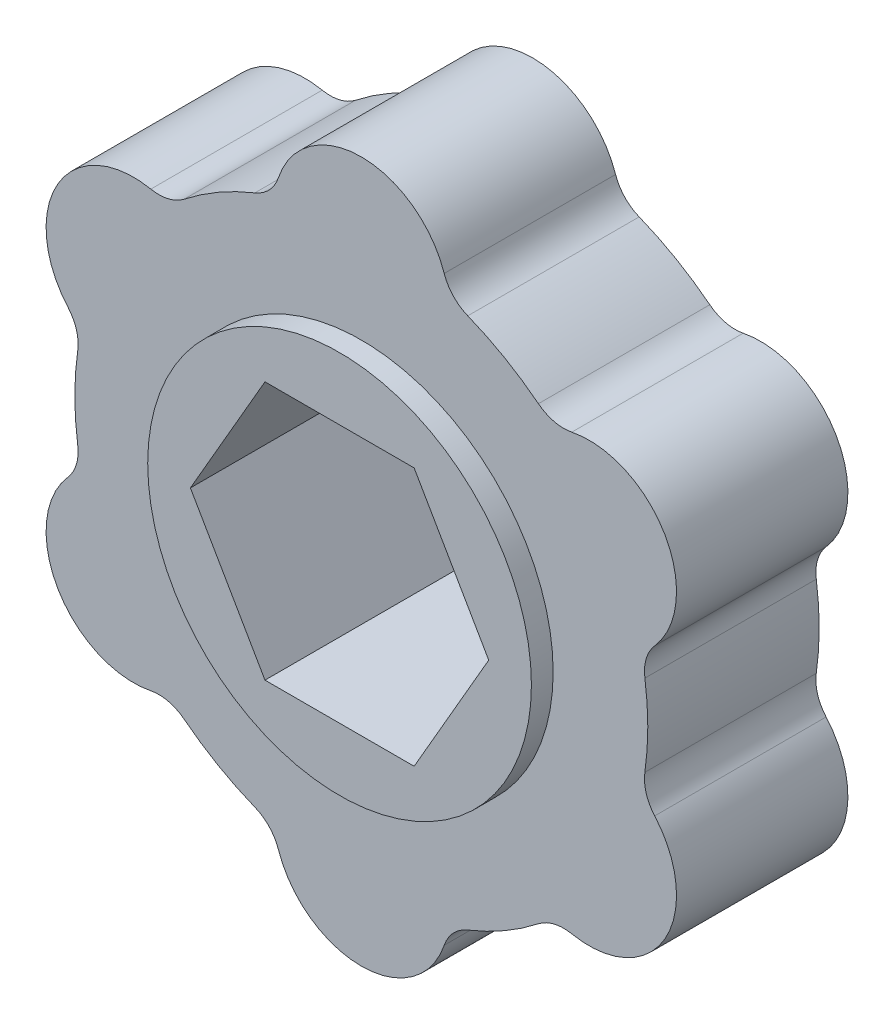
SolidWorks part; units mm, degrees
material "PET"
ref_plane "Front Plane" through (0, 0, 0) normal (0, 0, 1) x (1, 0, 0)
ref_plane "Top Plane" through (0, 0, 0) normal (0, 1, 0) x (1, 0, 0)
ref_plane "Right Plane" through (0, 0, 0) normal (1, 0, 0) x (0, 0, -1)
sketch "Sketch5" plane through (0, 0, 0) normal (0, 0, 1) x (1, 0, 0)
  line L0 (0, 0) -> (0, 13.0556) construction
  circle A0 centre (0, 0) radius 14.224
  circle A1 centre (0, 0) radius 17.399 construction
  arc A2 (-4.3147, 13.5538) -> (4.3147, 13.5538) centre (0, 13.0556) cw
  arc A3 (9.5806, 10.5136) -> (13.8953, 3.0402) centre (11.3065, 6.5278) cw
  arc A4 (13.8953, -3.0402) -> (9.5806, -10.5136) centre (11.3065, -6.5278) cw
  arc A5 (4.3147, -13.5538) -> (-4.3147, -13.5538) centre (0, -13.0556) cw
  arc A6 (-9.5806, -10.5136) -> (-13.8953, -3.0402) centre (-11.3065, -6.5278) cw
  arc A7 (-13.8953, 3.0402) -> (-9.5806, 10.5136) centre (-11.3065, 6.5278) cw
  point P24 (0, 0)
  dimension "D1" = 28.448
  dimension "D2" = 34.798
  dimension "D3" = 4.3434
  dimension "D4" = 6
extrude "Boss-Extrude2" add sketch "Sketch5" along normal blind 8.509 contours A7 A0 | A2 A0 | A3 A0 | A4 A0 | A5 A0 | A6 A0 | A0 region at (13.3495, 7.7073, 0) region at (13.3495, -7.7073, 0) region at (0, 15.4147, 0) region at (0, -15.4147, 0) region at (-13.3495, 7.7073, 0) region at (-13.3495, -7.7073, 0)
fillet "Fillet1" radius 2.032 12 edges at (-9.5806, 10.5136, 4.2545) (-4.3147, 13.5538, 4.2545) (4.3147, 13.5538, 4.2545) (9.5806, 10.5136, 4.2545) (13.8953, 3.0402, 4.2545) (13.8953, -3.0402, 4.2545) (9.5806, -10.5136, 4.2545) (4.3147, -13.5538, 4.2545) (-4.3147, -13.5538, 4.2545) (-9.5806, -10.5136, 4.2545) (-13.8953, -3.0402, 4.2545) (-13.8953, 3.0402, 4.2545)
sketch "Sketch6" plane through (0, 0, 8.509) normal (0, 0, 1) x (1, 0, 0)
  line L1 (7.4057, 0) -> (3.7028, 6.4135)
  line L2 (3.7028, 6.4135) -> (-3.7028, 6.4135)
  line L3 (-3.7028, 6.4135) -> (-7.4057, 0)
  line L4 (-7.4057, 0) -> (-3.7028, -6.4135)
  line L5 (-3.7028, -6.4135) -> (3.7028, -6.4135)
  line L6 (3.7028, -6.4135) -> (7.4057, 0)
  circle A0 centre (0, 0) radius 6.4135 construction
  dimension "D1" = 12.827
extrude "Cut-Extrude1" cut sketch "Sketch6" against normal through all
sketch "Sketch7" plane through (0, 0, 0) normal (0, 0, -1) x (-1, 0, 0)
  line L0 (-7.4057, 0) -> (-3.7028, 6.4135) construction
  line L1 (-3.7028, -6.4135) -> (-7.4057, 0) construction
  line L2 (3.7028, -6.4135) -> (-3.7028, -6.4135) construction
  line L3 (7.4057, 0) -> (3.7028, -6.4135) construction
  line L4 (3.7028, 6.4135) -> (7.4057, 0) construction
  line L5 (-3.7028, 6.4135) -> (3.7028, 6.4135) construction
  line L6 (-7.4057, 0) -> (-3.7028, 6.4135)
  line L7 (-3.7028, -6.4135) -> (-7.4057, 0)
  line L8 (3.7028, -6.4135) -> (-3.7028, -6.4135)
  line L9 (7.4057, 0) -> (3.7028, -6.4135)
  line L10 (3.7028, 6.4135) -> (7.4057, 0)
  line L11 (-3.7028, 6.4135) -> (3.7028, 6.4135)
  circle A0 centre (0, 0) radius 9.525
  dimension "D1" = 19.05
extrude "Boss-Extrude3" add sketch "Sketch7" along normal blind 1.0795
sketch "Sketch8" plane through (0, 0, 8.509) normal (0, 0, 1) x (1, 0, 0)
  line L1 (3.7028, -6.4135) -> (7.4057, 0)
  line L2 (7.4057, 0) -> (3.7028, 6.4135)
  line L3 (3.7028, 6.4135) -> (-3.7028, 6.4135)
  line L4 (-3.7028, 6.4135) -> (-7.4057, 0)
  line L5 (-7.4057, 0) -> (-3.7028, -6.4135)
  line L6 (-3.7028, -6.4135) -> (3.7028, -6.4135)
  circle A0 centre (0, 0) radius 9.525
  circle A1 centre (0, 0) radius 6.4135 construction
  dimension "D1" = 19.05
  dimension "D2" = 12.827
extrude "Boss-Extrude4" add sketch "Sketch8" along normal blind 1.0795
equation "\"D1@Boss-Extrude2\"=0.335000in"
equation "\"D1@Boss-Extrude3\"=0.21-(0.335/2)"
equation "\"D1@Boss-Extrude4\"=0.21-(0.335/2)"
